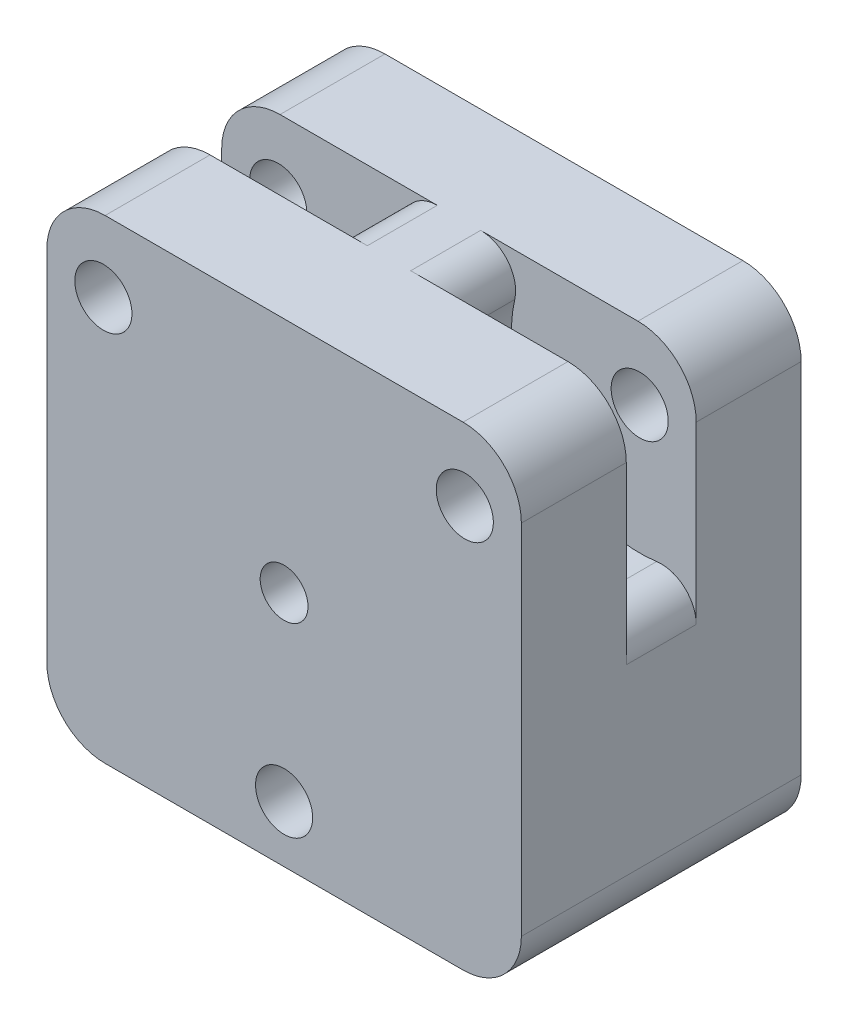
SolidWorks part; units mm, degrees
ref_plane "Front Plane" through (0, 0, 0) normal (0, 0, 1) x (1, 0, 0)
ref_plane "Top Plane" through (0, 0, 0) normal (0, 1, 0) x (1, 0, 0)
ref_plane "Right Plane" through (0, 0, 0) normal (1, 0, 0) x (0, 0, -1)
sketch "Sketch1" plane through (0, 0, 0) normal (0, 0, 1) x (1, 0, 0)
  line L0 (-15.5, 14.2005) -> (15.5, 14.2005) construction
  line L1 (-15.35, -20.35) -> (15.35, -20.35)
  line L2 (-20.35, -15.35) -> (-20.35, 15.35)
  line L3 (-15.35, 20.35) -> (15.35, 20.35)
  line L4 (20.35, -15.35) -> (20.35, 15.35)
  line L5 (-20.35, -20.35) -> (20.35, 20.35) construction
  line L6 (-20.35, 20.35) -> (20.35, -20.35) construction
  line L8 (-3, 23.25) -> (3, 23.25) construction
  line L9 (-3, 23.25) -> (-3, 8.25) construction
  line L10 (-3, 8.25) -> (3, 8.25) construction
  line L11 (3, 23.25) -> (3, 8.25) construction
  line L12 (-3, 23.25) -> (3, 8.25) construction
  line L13 (-3, 8.25) -> (3, 23.25) construction
  line L14 (-2.5, 1) -> (2.5, 1) construction
  line L15 (-2.5, 1) -> (-2.5, 8.25) construction
  line L16 (-2.5, 8.25) -> (2.5, 8.25) construction
  line L17 (2.5, 1) -> (2.5, 8.25) construction
  line L18 (-2.5, 1) -> (2.5, 8.25) construction
  line L19 (-2.5, 8.25) -> (2.5, 1) construction
  circle A0 centre (0, 0) radius 2.05
  circle A1 centre (-15.5, 14.2005) radius 2.45
  circle A2 centre (15.5, 14.2005) radius 2.45
  circle A3 centre (0, -15.5) radius 2.45
  circle A4 centre (0, 0) radius 1 construction
  arc A5 (-15.35, -20.35) -> (-20.35, -15.35) centre (-15.35, -15.35) cw
  arc A6 (15.35, -20.35) -> (20.35, -15.35) centre (15.35, -15.35) ccw
  arc A7 (15.35, 20.35) -> (20.35, 15.35) centre (15.35, 15.35) cw
  arc A8 (-20.35, 15.35) -> (-15.35, 20.35) centre (-15.35, 15.35) cw
  circle A9 centre (-15.5, 14.2005) radius 11
  circle A10 centre (15.5, 14.2005) radius 11
  circle A11 centre (0, -15.5) radius 11
  point P13 (0, 14.2005)
  point P16 (0, 15.75)
  point P21 (0, 4.625)
  dimension "D1" = 4.1
  dimension "D3" = 4.9
  dimension "D6" = 2.4
  dimension "D11" = 2
  dimension "D12" = 11
  dimension "D13" = 5
  dimension "D14" = 22
  dimension "D2" = 2.4
  dimension "D4" = 31
  dimension "D5" = 3.6995
  dimension "D7" = 6
  dimension "D8" = 15
  dimension "D9" = 7.25
  dimension "D10" = 5
extrude "Boss-Extrude1" add sketch "Sketch1" along normal blind 24 contours A1 | A3 | A2 | A8 L2 A5 L1 A6 L4 A7 L3 A3 A2 A1 A0 | L2 A9 L3 A8 A1 | L1 A11 A3 | L3 A10 L4 A7 A2 region at (0, -2.1498, 0) region at (-2.4282, -5.0495, 0) region at (-12.7157, 12.0602, 0) region at (12.7157, 12.0602, 0) region at (-15.5, 14.2005, 0) region at (15.5, 14.2005, 0) region at (0, -15.5, 0)
extrude "Cut-Extrude1" cut sketch "Sketch1<4>" against normal blind 6 from offset 15 contours A2 | A3 | A1 | L3 A9 L2 A8 | L2 A9 L3 A8 A1 | L3 A10 L4 A7 A2 | L4 A10 L3 A7 | L1 A11 A3 | L1 A11 region at (-2.4282, -5.0495, 0) region at (0, -22.8805, 0) region at (-23.5725, 21.239, 0) region at (-12.7157, 12.0602, 0) region at (18.6304, 24.4429, 0) region at (12.7157, 12.0602, 0) region at (-15.5, 14.2005, 0) region at (15.5, 14.2005, 0) region at (0, -15.5, 0)
sketch "Sketch1<4>" plane through (0, 0, 0) normal (0, 0, 1) x (1, 0, 0) same geometry as "Sketch1"
extrude "Cut-Extrude3" cut sketch "Sketch1<5>" along normal blind 44 contours A1 | A3 | A2 region at (-15.5, 14.2005, 0) region at (0, -15.5, 0)
sketch "Sketch1<5>" plane through (0, 0, 0) normal (0, 0, 1) x (1, 0, 0) same geometry as "Sketch1"
fillet "Fillet1" radius 3 6 edges at (-9.8731, -20.35, 12) (9.8731, -20.35, 12) (-20.35, 4.3274, 12) (20.35, 4.3274, 12) (-6.3795, 20.35, 12) (6.3795, 20.35, 12)
